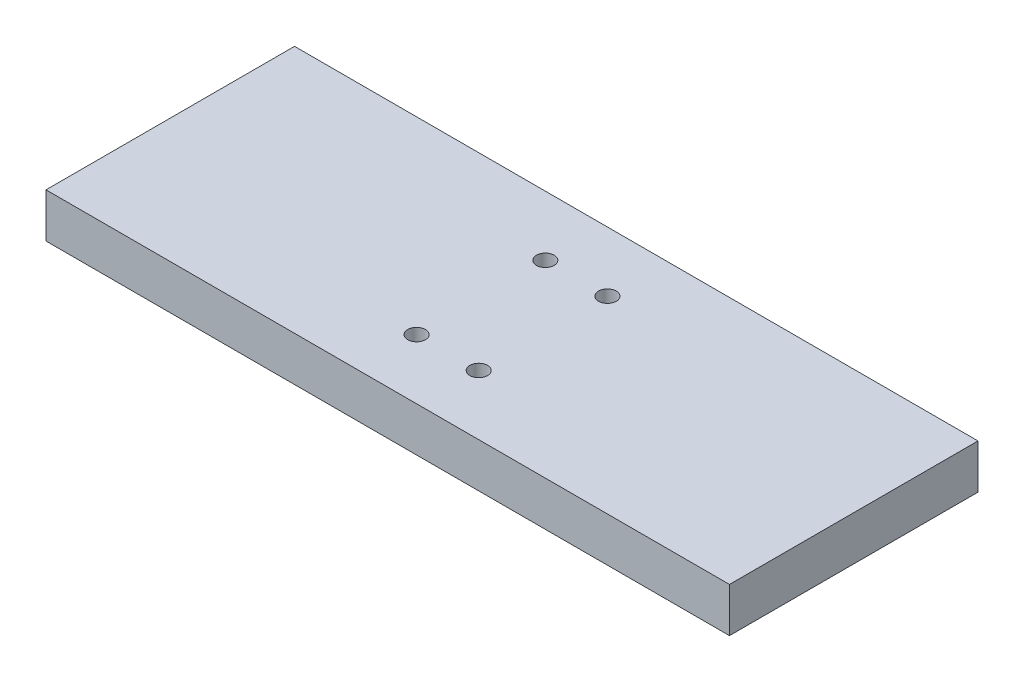
SolidWorks part; units mm, degrees
ref_plane "Front Plane" through (0, 0, 0) normal (0, 0, 1) x (1, 0, 0)
ref_plane "Top Plane" through (0, 0, 0) normal (0, 1, 0) x (1, 0, 0)
ref_plane "Right Plane" through (0, 0, 0) normal (1, 0, 0) x (0, 0, -1)
sketch "Sketch1" plane through (0, 0, 0) normal (0, 1, 0) x (1, 0, 0)
  line L1 (77, 28) -> (-77, 28)
  line L2 (77, 28) -> (77, -28)
  line L3 (77, -28) -> (-77, -28)
  line L4 (-77, 28) -> (-77, -28)
  line L5 (77, 28) -> (-77, -28) construction
  line L6 (77, -28) -> (-77, 28) construction
  point P0 (0, 0)
  dimension "D1" = 154
  dimension "D2" = 56
extrude "Boss-Extrude1" add sketch "Sketch1" along normal blind 10
sketch "Sketch4" plane through (0, 10, 0) normal (0, 1, 0) x (1, 0, 0)
  line L0 (77, 0) -> (-77, 0) construction
  line L1 (0, 28) -> (0, -28) construction
  line L2 (-77, 28) -> (-77, -28) construction
  line L3 (-77, -28) -> (77, -28) construction
  circle A0 centre (-27, 15) radius 2
  circle A1 centre (27, 15) radius 2
  circle A2 centre (27, -15) radius 2
  circle A3 centre (-27, -15) radius 2
  point P6 (0, 0)
  point P10 (0, 0)
  dimension "D1" = 4
  dimension "D2" = 27
  dimension "D3" = 15
hole_wizard "Ø4.0mm Dowel Hole3" positions "3DSketch3" profile "Sketch6" hole size "Ø4.0" standard "ANSI Metric"
sketch3d "3DSketch3"
  line L0 (0, 10, 28) -> (0, 10, -28) construction
  line L1 (-77, 10, 28) -> (77, 10, 28) construction
  line L2 (77, 10, -28) -> (-77, 10, -28) construction
  line L6 (-7, 10, -14.5) -> (-7, 10, 14.5) construction
  line L8 (-7, 10, 0) -> (0, 10, 0) construction
  point P0 (-7, 10, -14.5)
  point P2 (-7, 10, 14.5)
  point P4 (7, 10, 14.5)
  point P6 (7, 10, -14.5)
  dimension "D1" = 14
  dimension "D2" = 14
  dimension "D3" = 29
  dimension "D4" = 29
  dimension "D5" = 7
sketch "Sketch6" plane through (-7, 10, -14.5) normal (1, 0, 0) x (0, 0, 1)
  line L0 (0, 0) -> (0, 7.2017)
  line L1 (0, 7.2017) -> (2, 6)
  line L2 (2, 6) -> (2, 0)
  line L5 (2, 0) -> (0, 0)
  line L10 (0, 7.2017) -> (-2, 6) construction
  line L11 (0, -6.35) -> (0, 107.95) construction
  dimension "Hole Dia." = 4
  dimension "Hole Depth" = 6
  dimension "Drill Angle" = 118
